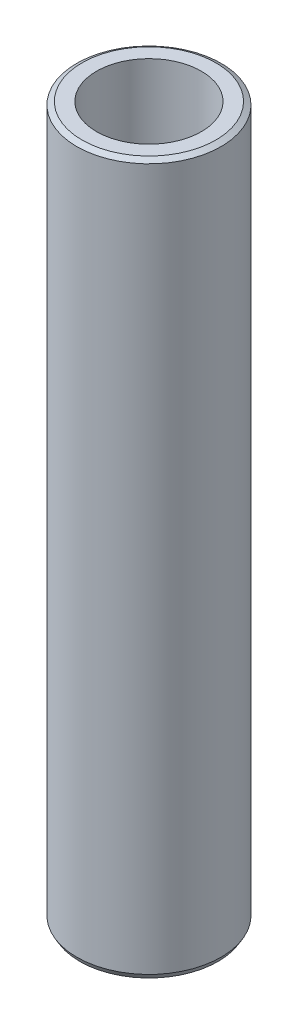
SolidWorks part; units mm, degrees
ref_plane "Front Plane" through (0, 0, 0) normal (0, 0, 1) x (1, 0, 0)
ref_plane "Top Plane" through (0, 0, 0) normal (0, 1, 0) x (1, 0, 0)
ref_plane "Right Plane" through (0, 0, 0) normal (1, 0, 0) x (0, 0, -1)
sketch "Sketch1" plane through (0, 0, 0) normal (0, 1, 0) x (1, 0, 0)
  circle A0 centre (0, 0) radius 60
  dimension "SHAFT_OD" = 120
extrude "Boss-Extrude1" add sketch "Sketch1" along normal blind 590.4749
sketch "Sketch2" plane through (0, 0, 0) normal (0, 1, 0) x (1, 0, 0)
  circle A0 centre (0, 0) radius 43.5764
  dimension "BORE_D" = 87.1528
extrude "Cut-Extrude1" cut sketch "Sketch2" along normal through all
chamfer "Chamfer1" distance 2.5234 angle 60 2 edges at (0, 590.4749, 60) (0, 0, 60) first distance on face at (0, 590.4749, 60) first distance on face at (0, 0, 43.5764)
